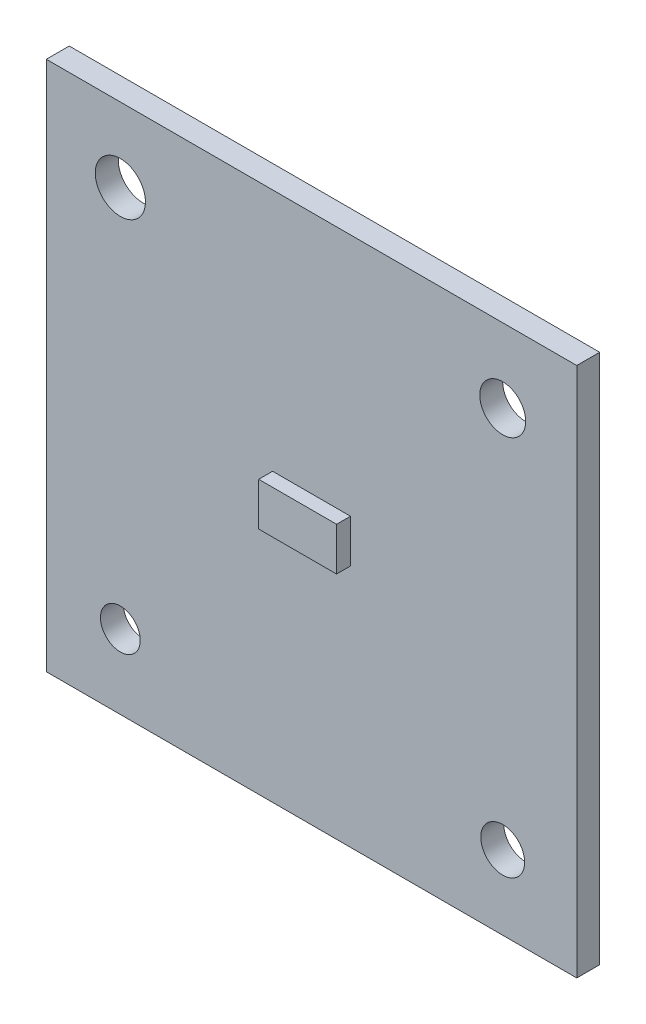
SolidWorks part; units mm, degrees
ref_plane "Front" through (0, 0, 0) normal (0, 0, 1) x (1, 0, 0)
ref_plane "Top" through (0, 0, 0) normal (0, 1, 0) x (1, 0, 0)
ref_plane "Right" through (0, 0, 0) normal (1, 0, 0) x (0, 0, -1)
sketch "Skizze1" plane through (0, 0, 0) normal (0, 0, 1) x (1, 0, 0)
  line L1 (-19.075, -19.075) -> (19.075, -19.075)
  line L2 (-19.075, -19.075) -> (-19.075, 19.075)
  line L3 (-19.075, 19.075) -> (19.075, 19.075)
  line L4 (19.075, -19.075) -> (19.075, 19.075)
  line L5 (-19.075, -19.075) -> (19.075, 19.075) construction
  line L6 (-19.075, 19.075) -> (19.075, -19.075) construction
  circle A0 centre (-13.75, 13.75) radius 1.8036
  circle A1 centre (13.75, 13.75) radius 1.6519
  circle A2 centre (13.75, -13.75) radius 1.5777
  circle A3 centre (-13.75, -13.75) radius 1.4312
  point P0 (0, 0)
  dimension "D1" = 38.15
  dimension "D2" = 27.5
extrude "Aufsatz-Linear austragen1" add sketch "Skizze1" along normal blind 1.65
sketch "Skizze2" plane through (0, 0, 1.65) normal (0, 0, 1) x (1, 0, 0)
  line L1 (-2.8, -1.55) -> (2.8, -1.55)
  line L2 (-2.8, -1.55) -> (-2.8, 1.55)
  line L3 (-2.8, 1.55) -> (2.8, 1.55)
  line L4 (2.8, -1.55) -> (2.8, 1.55)
  line L5 (-2.8, -1.55) -> (2.8, 1.55) construction
  line L6 (-2.8, 1.55) -> (2.8, -1.55) construction
  point P0 (0, 0)
  dimension "D1" = 5.6
  dimension "D2" = 3.1
extrude "Aufsatz-Linear austragen2" add sketch "Skizze2" along normal blind 1
sketch "Sketch1" plane through (0, 0, 1.65) normal (0, 0, 1) x (1, 0, 0)
  circle A0 centre (0, 0) radius 5
  dimension "D1" = 10
